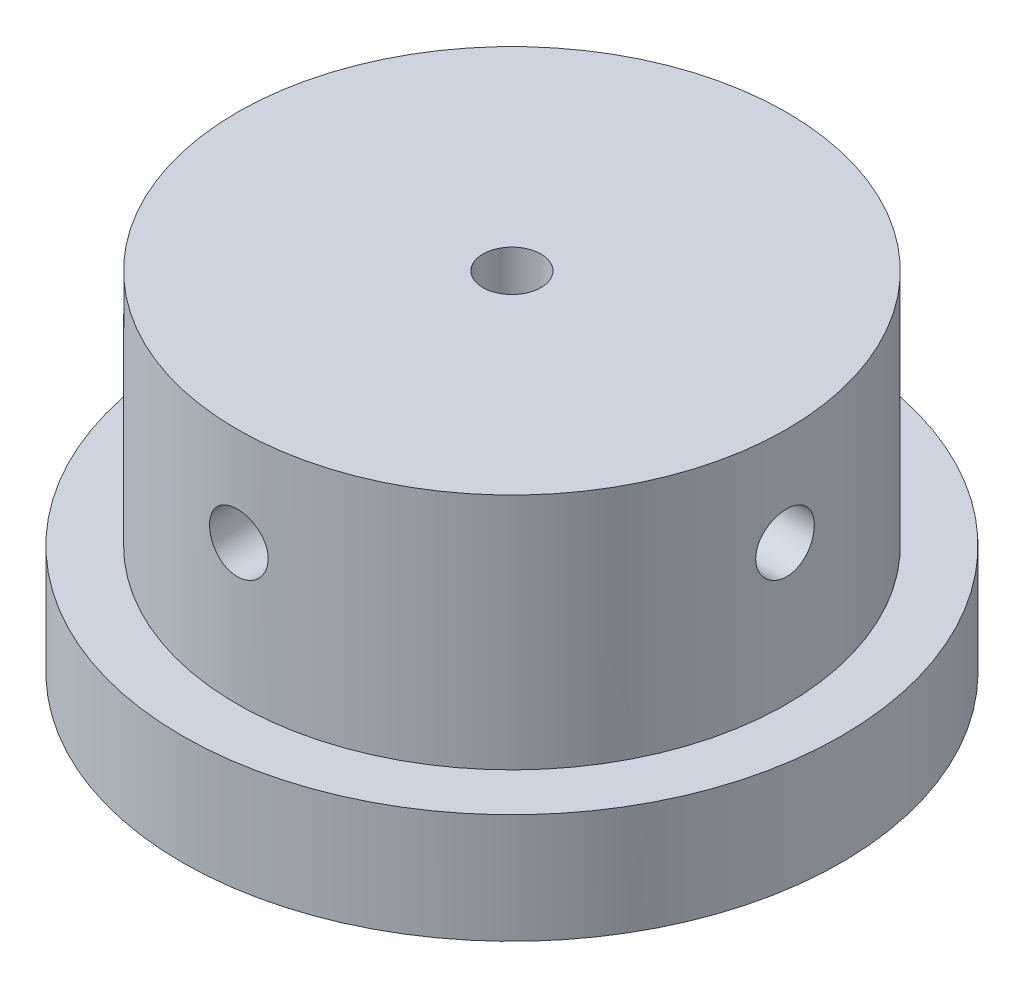
SolidWorks part; units mm, degrees
ref_plane "Front Plane" through (0, 0, 0) normal (0, 0, 1) x (1, 0, 0)
ref_plane "Top Plane" through (0, 0, 0) normal (0, 1, 0) x (1, 0, 0)
ref_plane "Right Plane" through (0, 0, 0) normal (1, 0, 0) x (0, 0, -1)
sketch "Sketch1" plane through (0, 0, 0) normal (0, 1, 0) x (1, 0, 0)
  circle A0 centre (0, 0) radius 15
  dimension "D1" = 30
extrude "Boss-Extrude1" add sketch "Sketch1" along normal blind 2
sketch "Sketch2" plane through (0, 2, 0) normal (0, 1, 0) x (1, 0, 0)
  circle A0 centre (0, 0) radius 13.5
  circle A1 centre (0, 0) radius 15
  circle A2 centre (0, 0) radius 15
  dimension "D1" = 0
  dimension "D2" = 1.5
extrude "Boss-Extrude2" add sketch "Sketch2" against normal up to surface (13 mm away)
sketch "Sketch3" plane through (0, -11, 0) normal (0, -1, 0) x (1, 0, 0)
  circle A0 centre (0, 0) radius 13.5 construction
  circle A1 centre (0, 0) radius 13.5
  circle A2 centre (0, 0) radius 18
  dimension "D1" = 36
extrude "Boss-Extrude3" add sketch "Sketch3" along normal up to surface (2 mm away)
sketch "Sketch4" plane through (0, -13, 0) normal (0, -1, 0) x (1, 0, 0)
  circle A0 centre (0, 0) radius 16.1
  circle A1 centre (0, 0) radius 18
  circle A2 centre (0, 0) radius 18
  dimension "D2" = 32.2
  dimension "D1" = 0
extrude "Boss-Extrude4" add sketch "Sketch4" along normal up to surface (3.9878 mm away)
chamfer "Chamfer1" distance 1 angle 45 1 edges at (0, -13, 13.5)
sketch "Sketch5" plane through (0, 2, 0) normal (0, 1, 0) x (1, 0, 0)
  circle A0 centre (0, 0) radius 13.5
  circle A1 centre (0, 0) radius 13.5 construction
extrude "Boss-Extrude5" add sketch "Sketch5" against normal up to surface (8.7338 mm away)
sketch "Sketch6" plane through (0, 2, 0) normal (0, 1, 0) x (1, 0, 0)
  circle A0 centre (0, 0) radius 1.5875
  dimension "D1" = 3.175
extrude "Cut-Extrude1" cut sketch "Sketch6" against normal through all both and the other way through all
sketch "Sketch7" plane through (0, 0, 0) normal (1, 0, 0) x (0, 0, -1)
  line L0 (0, 0) -> (0, -6.7338) construction
  line L1 (-1.5875, -6.7338) -> (1.5875, -6.7338) construction
  circle A0 centre (0, -3.3669) radius 1.6
  dimension "D1" = 3.2
extrude "Cut-Extrude2" cut sketch "Sketch7" against normal through all
ref_axis "Axis1" through (0, -12, 0) along (0, 1, 0)
ref_plane "Plane2" through (-10, 0, 0) normal (1, 0, 0) x (0, 0, -1)
ref_plane "Plane3" through (-9, 0, 0) normal (1, 0, 0) x (0, 0, -1)
sketch "Sketch11" plane through (-10, 0, 0) normal (1, 0, 0) x (0, 0, -1)
  circle A0 centre (0, -3.3669) radius 1.6 construction
  circle A1 centre (0, -3.3669) radius 1.6 construction
  circle A2 centre (0, -3.3669) radius 2
  dimension "D1" = 4
extrude "Cut-Extrude7" [suppressed] cut sketch "Sketch11" along normal blind 5.5
sketch "Sketch12" plane through (-10, 0, 0) normal (1, 0, 0) x (0, 0, -1)
  circle A0 centre (0, -3.3669) radius 3.5
  dimension "D1" = 7
extrude "Cut-Extrude8" [suppressed] cut sketch "Sketch12" against normal blind 5
chamfer "Chamfer2" [suppressed] distance 1 angle 45
pattern_circular "CirPattern3" count 4 over 360 about axis through (0, -12, 0) along (0, 1, 0) of "Cut-Extrude2", "Cut-Extrude7", "Cut-Extrude8", "Chamfer2"
sketch "Sketch13" plane through (-9, 0, 0) normal (1, 0, 0) x (0, 0, -1)
  line L0 (-2.75, -4.9546) -> (-2.75, -6.7338)
  line L1 (0, -6.5423) -> (2.75, -4.9546) construction
  line L2 (2.75, -4.9546) -> (2.75, -1.7792)
  line L3 (2.75, -1.7792) -> (0, -0.1915)
  line L4 (0, -0.1915) -> (-2.75, -1.7792)
  line L5 (-2.75, -1.7792) -> (-2.75, -4.9546)
  line L6 (-2.75, -4.9546) -> (0, -6.5423) construction
  line L7 (-2.75, -6.7338) -> (2.75, -6.7338)
  line L8 (2.75, -6.7338) -> (2.75, -4.9546)
  line L9 (-1.5875, -6.7338) -> (1.5875, -6.7338) construction
  circle A0 centre (0, -3.3669) radius 2.75 construction
  circle A1 centre (0, -3.3669) radius 1.6 construction
  dimension "D1" = 5.5
extrude "Cut-Extrude9" cut sketch "Sketch13" along normal blind 3
pattern_circular "CirPattern4" count 4 over 360 about axis through (0, -12, 0) along (0, 1, 0) of "Cut-Extrude9"
